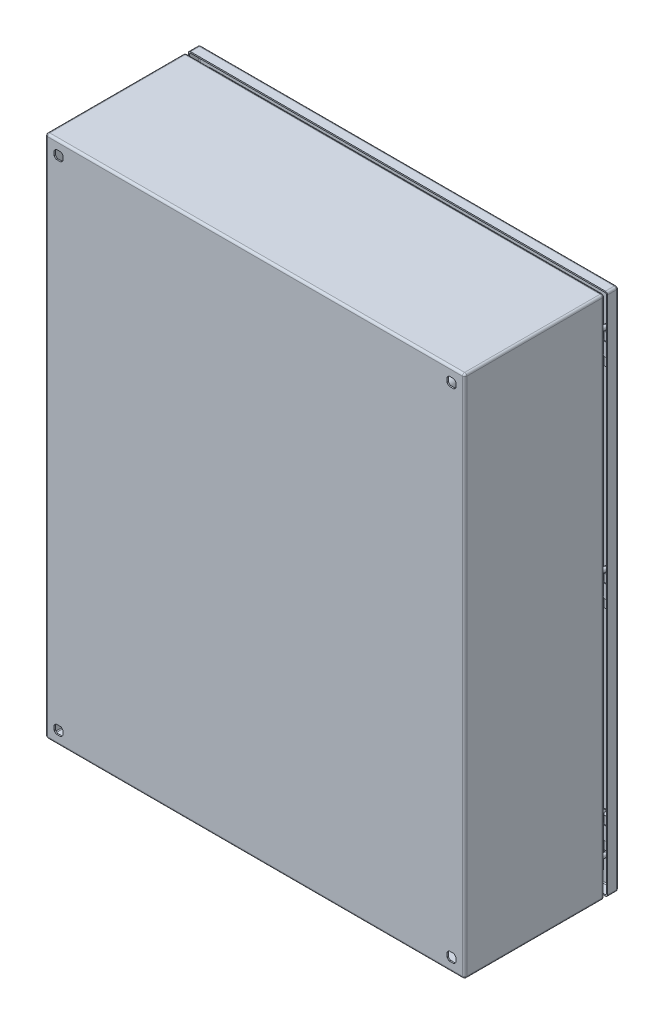
SolidWorks part; units mm, degrees
ref_plane "Front Plane" through (0, 0, 0) normal (0, 0, 1) x (1, 0, 0)
ref_plane "Top Plane" through (0, 0, 0) normal (0, 1, 0) x (1, 0, 0)
ref_plane "Right Plane" through (0, 0, 0) normal (1, 0, 0) x (0, 0, -1)
sketch "Sketch1" plane through (0, 0, 0) normal (0, 0, 1) x (1, 0, 0)
  line L0 (-304.8, -381) -> (304.8, 381) construction
  line L1 (-304.8, 381) -> (304.8, 381)
  line L2 (-304.8, 381) -> (-304.8, -381)
  line L3 (-304.8, -381) -> (304.8, -381)
  line L4 (304.8, 381) -> (304.8, -381)
  line L5 (-258.826, 381) -> (-258.826, -381) construction
  line L6 (-279.4, 355.6) -> (279.4, -355.6) construction
  line L7 (-279.4, 355.6) -> (279.4, 355.6)
  line L8 (-279.4, 355.6) -> (-279.4, -355.6)
  line L9 (-279.4, -355.6) -> (279.4, -355.6)
  line L10 (279.4, 355.6) -> (279.4, -355.6)
  line L11 (221.996, 0) -> (0, 0) construction
  line L12 (-188.214, 321.691) -> (221.996, 321.691)
  line L13 (-188.214, 321.691) -> (-188.214, -321.691)
  line L14 (-188.214, -321.691) -> (221.996, -321.691)
  line L15 (221.996, 321.691) -> (221.996, -321.691)
  line L16 (0, -361.95) -> (0, 361.95) construction
  line L17 (-289.0088, 368.3) -> (-282.4912, 368.3)
  line L18 (-292.1, 365.2088) -> (-292.1, 358.6912)
  line L19 (-289.0088, 355.6) -> (-282.4912, 355.6)
  line L20 (-279.4, 365.2088) -> (-279.4, 358.6912)
  line L21 (-285.75, 361.95) -> (285.75, 361.95) construction
  line L22 (-285.75, 361.95) -> (-285.75, -361.95) construction
  line L23 (-285.75, -361.95) -> (285.75, -361.95) construction
  line L24 (285.75, 361.95) -> (285.75, -361.95) construction
  line L25 (-285.75, 0) -> (285.75, 0) construction
  line L26 (279.4, 365.2088) -> (279.4, 358.6912)
  line L27 (289.0088, 355.6) -> (282.4912, 355.6)
  line L28 (292.1, 365.2088) -> (292.1, 358.6912)
  line L29 (289.0088, 368.3) -> (282.4912, 368.3)
  line L30 (289.0088, -368.3) -> (282.4912, -368.3)
  line L31 (292.1, -365.2088) -> (292.1, -358.6912)
  line L32 (289.0088, -355.6) -> (282.4912, -355.6)
  line L33 (279.4, -365.2088) -> (279.4, -358.6912)
  line L34 (-279.4, -365.2088) -> (-279.4, -358.6912)
  line L35 (-289.0088, -355.6) -> (-282.4912, -355.6)
  line L36 (-292.1, -365.2088) -> (-292.1, -358.6912)
  line L37 (-289.0088, -368.3) -> (-282.4912, -368.3)
  line L38 (-269.113, -345.313) -> (269.113, -345.313) construction
  line L39 (0, -345.313) -> (0, 0) construction
  line L40 (-269.113, -345.313) -> (-269.113, 345.313) construction
  line L41 (-269.113, 0) -> (0, 0) construction
  arc A0 (-289.0088, 368.3) -> (-292.1, 365.2088) centre (-285.75, 361.95) ccw
  arc A1 (-292.1, 358.6912) -> (-289.0088, 355.6) centre (-285.75, 361.95) ccw
  arc A2 (-282.4912, 355.6) -> (-279.4, 358.6912) centre (-285.75, 361.95) ccw
  arc A3 (-279.4, 365.2088) -> (-282.4912, 368.3) centre (-285.75, 361.95) ccw
  arc A4 (279.4, 365.2088) -> (282.4912, 368.3) centre (285.75, 361.95) cw
  arc A5 (282.4912, 355.6) -> (279.4, 358.6912) centre (285.75, 361.95) cw
  arc A6 (292.1, 358.6912) -> (289.0088, 355.6) centre (285.75, 361.95) cw
  arc A7 (289.0088, 368.3) -> (292.1, 365.2088) centre (285.75, 361.95) cw
  arc A8 (289.0088, -368.3) -> (292.1, -365.2088) centre (285.75, -361.95) ccw
  arc A9 (292.1, -358.6912) -> (289.0088, -355.6) centre (285.75, -361.95) ccw
  arc A10 (282.4912, -355.6) -> (279.4, -358.6912) centre (285.75, -361.95) ccw
  arc A11 (279.4, -365.2088) -> (282.4912, -368.3) centre (285.75, -361.95) ccw
  arc A12 (-279.4, -365.2088) -> (-282.4912, -368.3) centre (-285.75, -361.95) cw
  arc A13 (-282.4912, -355.6) -> (-279.4, -358.6912) centre (-285.75, -361.95) cw
  arc A14 (-292.1, -358.6912) -> (-289.0088, -355.6) centre (-285.75, -361.95) cw
  arc A15 (-289.0088, -368.3) -> (-292.1, -365.2088) centre (-285.75, -361.95) cw
  circle A16 centre (-269.113, 345.313) radius 3.9688
  circle A17 centre (269.113, 345.313) radius 3.9688
  circle A18 centre (-269.113, -345.313) radius 3.9688
  circle A19 centre (269.113, -345.313) radius 3.9688
  point P7 (-304.8, 0)
  point P8 (-304.8, 304.8)
  point P9 (-304.8, -304.8)
  dimension "D5" = 14.2748
  dimension "D10" = 82.804
  dimension "D11" = 45.974
  dimension "D12" = 7.9375
  dimension "B" = 609.6
  dimension "D2" = 76.2
  dimension "A" = 762
  dimension "D3" = 76.2
  dimension "D4" = 12.7
  dimension "Panel Width" = 558.8
  dimension "Panel Height" = 711.2
  dimension "H" = 410.21
  dimension "G" = 643.382
  dimension "D6" = 538.226
  dimension "D7" = 690.626
  dimension "D8" = 19.05
  dimension "D9" = 19.05
  dimension "D13" = 116.586
sketch "Sketch2" plane through (0, 0, 0) normal (0, 1, 0) x (1, 0, 0)
  line L0 (0, 0) -> (0, 203.2) construction
  line L1 (0, 203.2) -> (0, 223.901) construction
  point P3 (0, 201.295)
  point P4 (0, 223.901)
  point P5 (0, 219.6148)
  point P7 (0, 214.2127)
  dimension "D1" = 22.606
  dimension "C" = 203.2
  dimension "wall thickness" = 1.905
  dimension "D3" = 4.2862
  dimension "D4" = 12.9177
sketch "Sketch3" plane through (0, 0, 0) normal (0, 0, 1) x (1, 0, 0)
  line L0 (-304.8, 381) -> (-304.8, -381) construction
  line L1 (-304.8, 381) -> (304.8, 381) construction
  line L2 (304.8, 381) -> (304.8, -381) construction
  line L3 (-304.8, -381) -> (304.8, -381) construction
  line L4 (-304.8, 381) -> (-304.8, -381)
  line L5 (-304.8, 381) -> (304.8, 381)
  line L6 (304.8, 381) -> (304.8, -381)
  line L7 (-304.8, -381) -> (304.8, -381)
extrude "Extrude1" add sketch "Sketch3" against normal up to vertex (203.2 mm away) up to point (0, 0, -203.2)
sketch "Sketch4" plane through (0, 0, -203.2) normal (0, 0, -1) x (-1, 0, 0)
  line L4 (285.877, 362.077) -> (-285.877, 362.077)
  line L5 (-285.877, 362.077) -> (-285.877, -362.077)
  line L6 (-285.877, -362.077) -> (285.877, -362.077)
  line L7 (285.877, -362.077) -> (285.877, 362.077)
  line L8 (283.972, 360.172) -> (-283.972, 360.172)
  line L9 (-283.972, 360.172) -> (-283.972, -360.172)
  line L10 (-283.972, -360.172) -> (283.972, -360.172)
  line L11 (283.972, -360.172) -> (283.972, 360.172)
  line L12 (283.972, 360.172) -> (-283.972, 360.172) construction
  line L13 (-283.972, 360.172) -> (-283.972, -360.172) construction
  line L14 (-283.972, -360.172) -> (283.972, -360.172) construction
  line L15 (283.972, -360.172) -> (283.972, 360.172) construction
  dimension "D1" = 20.828
  dimension "D2" = 1.905
extrude "Extrude2" add sketch "Sketch4" along normal up to vertex (11.0127 mm away) up to point (0, 0, -214.2127)
sketch "Sketch5" plane through (0, 0, -214.2127) normal (0, 0, -1) x (-1, 0, 0)
  line L4 (285.877, -362.077) -> (285.877, 362.077)
  line L5 (285.877, 362.077) -> (-285.877, 362.077)
  line L6 (-285.877, 362.077) -> (-285.877, -362.077)
  line L7 (-285.877, -362.077) -> (285.877, -362.077)
  line L8 (285.877, -362.077) -> (285.877, 362.077)
  line L9 (285.877, 362.077) -> (-285.877, 362.077)
  line L10 (-285.877, 362.077) -> (-285.877, -362.077)
  line L11 (-285.877, -362.077) -> (285.877, -362.077)
  dimension "D1" = 0
extrude "Extrude3" add sketch "Sketch5" along normal up to vertex (5.402 mm away) draft 13 up to point (0, 0, -219.6148) draft outward yes
fillet "Fillet1" radius 3.175 20 edges at (304.8, 0, 0) (0, -381, 0) (-304.8, 0, 0) (0, 381, 0) (285.877, -362.077, -208.7064) (286.5006, -362.7006, -216.9137) (-285.877, -362.077, -208.7064) (-286.5006, -362.7006, -216.9137) (286.5006, 362.7006, -216.9137) (285.877, 362.077, -208.7064) (-286.5006, 362.7006, -216.9137) (-285.877, 362.077, -208.7064) (0, -381, -203.2) (304.8, 0, -203.2) (0, 381, -203.2) (-304.8, 0, -203.2) (-304.8, 381, -101.6) (304.8, 381, -101.6) (-304.8, -381, -101.6) (304.8, -381, -101.6)
fillet "Fillet2" radius 1.5875 8 edges at (-284.9471, -361.1471, -203.2) (0, -362.077, -203.2) (284.9471, -361.1471, -203.2) (285.877, 0, -203.2) (284.9471, 361.1471, -203.2) (0, 362.077, -203.2) (-284.9471, 361.1471, -203.2) (-285.877, 0, -203.2)
shell "Shell1" thickness 1.905
sketch "Sketch6" plane through (0, 0, -1.905) normal (0, 0, -1) x (-1, 0, 0)
  line L0 (292.1, 365.2088) -> (292.1, 358.6912) construction
  line L1 (289.0088, 368.3) -> (282.4912, 368.3) construction
  line L2 (-279.4, 365.2088) -> (-279.4, 358.6912) construction
  line L3 (-289.0088, 355.6) -> (-282.4912, 355.6) construction
  line L4 (-292.1, 365.2088) -> (-292.1, 358.6912) construction
  line L5 (-289.0088, 368.3) -> (-282.4912, 368.3) construction
  line L6 (292.1, 365.2088) -> (292.1, 358.6912)
  line L7 (289.0088, 368.3) -> (282.4912, 368.3)
  line L8 (-279.4, 365.2088) -> (-279.4, 358.6912)
  line L9 (-289.0088, 355.6) -> (-282.4912, 355.6)
  line L10 (-292.1, 365.2088) -> (-292.1, 358.6912)
  line L11 (-289.0088, 368.3) -> (-282.4912, 368.3)
  line L12 (279.4, 365.2088) -> (279.4, 358.6912) construction
  line L13 (289.0088, 355.6) -> (282.4912, 355.6) construction
  line L14 (279.4, 365.2088) -> (279.4, 358.6912)
  line L15 (289.0088, 355.6) -> (282.4912, 355.6)
  line L16 (279.4, -365.2088) -> (279.4, -358.6912) construction
  line L17 (289.0088, -355.6) -> (282.4912, -355.6) construction
  line L18 (292.1, -365.2088) -> (292.1, -358.6912) construction
  line L19 (289.0088, -368.3) -> (282.4912, -368.3) construction
  line L20 (279.4, -365.2088) -> (279.4, -358.6912)
  line L21 (289.0088, -355.6) -> (282.4912, -355.6)
  line L22 (292.1, -365.2088) -> (292.1, -358.6912)
  line L23 (289.0088, -368.3) -> (282.4912, -368.3)
  line L24 (-289.0088, -368.3) -> (-282.4912, -368.3) construction
  line L25 (-279.4, -365.2088) -> (-279.4, -358.6912) construction
  line L26 (-289.0088, -355.6) -> (-282.4912, -355.6) construction
  line L27 (-292.1, -365.2088) -> (-292.1, -358.6912) construction
  line L28 (-289.0088, -368.3) -> (-282.4912, -368.3)
  line L29 (-279.4, -365.2088) -> (-279.4, -358.6912)
  line L30 (-289.0088, -355.6) -> (-282.4912, -355.6)
  line L31 (-292.1, -365.2088) -> (-292.1, -358.6912)
  arc A0 (289.0088, 355.6) -> (292.1, 358.6912) centre (285.75, 361.95) ccw construction
  arc A1 (282.4912, 368.3) -> (279.4, 365.2088) centre (285.75, 361.95) ccw construction
  arc A2 (-282.4912, 355.6) -> (-279.4, 358.6912) centre (-285.75, 361.95) ccw construction
  arc A3 (-292.1, 358.6912) -> (-289.0088, 355.6) centre (-285.75, 361.95) ccw construction
  arc A4 (-289.0088, 368.3) -> (-292.1, 365.2088) centre (-285.75, 361.95) ccw construction
  arc A5 (289.0088, 355.6) -> (292.1, 358.6912) centre (285.75, 361.95) ccw
  arc A6 (282.4912, 368.3) -> (279.4, 365.2088) centre (285.75, 361.95) ccw
  arc A7 (-282.4912, 355.6) -> (-279.4, 358.6912) centre (-285.75, 361.95) ccw
  arc A8 (-292.1, 358.6912) -> (-289.0088, 355.6) centre (-285.75, 361.95) ccw
  arc A9 (-289.0088, 368.3) -> (-292.1, 365.2088) centre (-285.75, 361.95) ccw
  arc A10 (279.4, 358.6912) -> (282.4912, 355.6) centre (285.75, 361.95) ccw construction
  arc A11 (292.1, 365.2088) -> (289.0088, 368.3) centre (285.75, 361.95) ccw construction
  arc A12 (279.4, 358.6912) -> (282.4912, 355.6) centre (285.75, 361.95) ccw
  arc A13 (292.1, 365.2088) -> (289.0088, 368.3) centre (285.75, 361.95) ccw
  arc A14 (282.4912, -355.6) -> (279.4, -358.6912) centre (285.75, -361.95) ccw construction
  arc A15 (292.1, -358.6912) -> (289.0088, -355.6) centre (285.75, -361.95) ccw construction
  arc A16 (289.0088, -368.3) -> (292.1, -365.2088) centre (285.75, -361.95) ccw construction
  arc A17 (279.4, -365.2088) -> (282.4912, -368.3) centre (285.75, -361.95) ccw construction
  arc A18 (282.4912, -355.6) -> (279.4, -358.6912) centre (285.75, -361.95) ccw
  arc A19 (292.1, -358.6912) -> (289.0088, -355.6) centre (285.75, -361.95) ccw
  arc A20 (289.0088, -368.3) -> (292.1, -365.2088) centre (285.75, -361.95) ccw
  arc A21 (279.4, -365.2088) -> (282.4912, -368.3) centre (285.75, -361.95) ccw
  arc A22 (-282.4912, -368.3) -> (-279.4, -365.2088) centre (-285.75, -361.95) ccw construction
  arc A23 (-279.4, -358.6912) -> (-282.4912, -355.6) centre (-285.75, -361.95) ccw construction
  arc A24 (-289.0088, -355.6) -> (-292.1, -358.6912) centre (-285.75, -361.95) ccw construction
  arc A25 (-292.1, -365.2088) -> (-289.0088, -368.3) centre (-285.75, -361.95) ccw construction
  arc A26 (-282.4912, -368.3) -> (-279.4, -365.2088) centre (-285.75, -361.95) ccw
  arc A27 (-279.4, -358.6912) -> (-282.4912, -355.6) centre (-285.75, -361.95) ccw
  arc A28 (-289.0088, -355.6) -> (-292.1, -358.6912) centre (-285.75, -361.95) ccw
  arc A29 (-292.1, -365.2088) -> (-289.0088, -368.3) centre (-285.75, -361.95) ccw
  arc A30 (-279.4, 365.2088) -> (-282.4912, 368.3) centre (-285.75, 361.95) ccw construction
  arc A31 (-279.4, 365.2088) -> (-282.4912, 368.3) centre (-285.75, 361.95) ccw
extrude "Cut-Extrude1" cut sketch "Sketch6" against normal through all
ref_plane "Plane1" through (0, 0, -23.876) normal (0, 0, 1) x (1, 0, 0)
sketch "Sketch7" plane through (0, 0, -23.876) normal (0, 0, 1) x (1, 0, 0)
  line L0 (-279.4, -355.6) -> (279.4, -355.6) construction
  line L1 (-279.4, 355.6) -> (-279.4, -355.6) construction
  line L2 (-279.4, 355.6) -> (279.4, 355.6) construction
  line L3 (279.4, 355.6) -> (279.4, -355.6) construction
  line L4 (-279.4, -355.6) -> (279.4, -355.6)
  line L5 (-279.4, 355.6) -> (-279.4, -355.6)
  line L6 (-279.4, 355.6) -> (279.4, 355.6)
  line L7 (279.4, 355.6) -> (279.4, -355.6)
  circle A0 centre (269.113, -345.313) radius 3.9688 construction
  circle A1 centre (-269.113, -345.313) radius 3.9688 construction
  circle A2 centre (-269.113, 345.313) radius 3.9688 construction
  circle A3 centre (269.113, 345.313) radius 3.9688 construction
  circle A4 centre (269.113, -345.313) radius 3.9688
  circle A5 centre (-269.113, -345.313) radius 3.9688
  circle A6 centre (-269.113, 345.313) radius 3.9688
  circle A7 centre (269.113, 345.313) radius 3.9688
extrude "Extrude4" add sketch "Sketch7" against normal blind 1.524
sketch "Sketch8" plane through (0, 0, -1.905) normal (0, 0, -1) x (-1, 0, 0)
  circle A0 centre (-269.113, 345.313) radius 7.9375
  circle A1 centre (269.113, 345.313) radius 7.9375
  circle A2 centre (269.113, -345.313) radius 7.9375
  circle A3 centre (-269.113, -345.313) radius 7.9375
  circle A4 centre (-269.113, 345.313) radius 3.9688 construction
  circle A5 centre (269.113, 345.313) radius 3.9688 construction
  circle A6 centre (-269.113, 345.313) radius 3.9688
  circle A7 centre (269.113, 345.313) radius 3.9688
  circle A8 centre (269.113, -345.313) radius 3.9688 construction
  circle A9 centre (269.113, -345.313) radius 3.9688
  circle A10 centre (-269.113, -345.313) radius 3.9688 construction
  circle A11 centre (-269.113, -345.313) radius 3.9688
  dimension "D1" = 15.875
extrude "Extrude5" add sketch "Sketch8" along normal up to surface (21.971 mm away) up to plane "Plane1"
ref_plane "Plane2" through (0, 0, -223.901) normal (0, 0, 1) x (1, 0, 0)
sketch "Sketch9" plane through (0, 0, -223.901) normal (0, 0, 1) x (1, 0, 0)
  line L0 (-304.8, -381) -> (304.8, -381) construction
  line L1 (304.8, 381) -> (304.8, -381) construction
  line L2 (-304.8, 381) -> (-304.8, -381) construction
  line L3 (-304.8, 381) -> (304.8, 381) construction
  line L4 (-304.8, -381) -> (304.8, -381)
  line L5 (304.8, 381) -> (304.8, -381)
  line L6 (-304.8, 381) -> (-304.8, -381)
  line L7 (-304.8, 381) -> (304.8, 381)
extrude "Extrude6" add sketch "Sketch9" along normal blind 16.002 separate body
fillet "Fillet3" radius 3.175 8 edges at (0, -381, -223.901) (304.8, 0, -223.901) (0, 381, -223.901) (-304.8, 0, -223.901) (304.8, -381, -215.9) (-304.8, -381, -215.9) (304.8, 381, -215.9) (-304.8, 381, -215.9)
shell "Shell2" thickness 1.905
sketch "Sketch10" plane through (0, 0, -221.996) normal (0, 0, 1) x (1, 0, 0)
  line L0 (-188.214, -321.691) -> (221.996, -321.691) construction
  line L1 (221.996, 321.691) -> (221.996, -321.691) construction
  line L2 (-188.214, 321.691) -> (221.996, 321.691) construction
  line L3 (-188.214, 321.691) -> (-188.214, -321.691) construction
  line L4 (-181.864, -321.691) -> (215.646, -321.691)
  line L5 (221.996, 315.341) -> (221.996, -315.341)
  line L6 (-181.864, 321.691) -> (215.646, 321.691)
  line L7 (-188.214, 315.341) -> (-188.214, -315.341)
  arc A0 (-181.864, 321.691) -> (-188.214, 315.341) centre (-181.864, 315.341) ccw
  arc A1 (221.996, 315.341) -> (215.646, 321.691) centre (215.646, 315.341) ccw
  arc A2 (215.646, -321.691) -> (221.996, -315.341) centre (215.646, -315.341) ccw
  arc A3 (-181.864, -321.691) -> (-188.214, -315.341) centre (-181.864, -315.341) cw
  dimension "D1" = 6.35
extrude "Cut-Extrude2" cut sketch "Sketch10" against normal through all
sketch "Sketch11" plane through (0, 0, -223.901) normal (0, 0, -1) x (-1, 0, 0)
  line L8 (181.864, 321.183) -> (-215.646, 321.183)
  line L9 (-221.488, 315.341) -> (-221.488, -315.341)
  line L10 (-215.646, -321.183) -> (181.864, -321.183)
  line L11 (187.706, -315.341) -> (187.706, 315.341)
  line L12 (181.864, 321.183) -> (-215.646, 321.183)
  line L13 (-221.488, 315.341) -> (-221.488, -315.341)
  line L14 (-215.646, -321.183) -> (181.864, -321.183)
  line L15 (187.706, -315.341) -> (187.706, 315.341)
  arc A8 (-215.646, 321.183) -> (-221.488, 315.341) centre (-215.646, 315.341) ccw
  arc A9 (-221.488, -315.341) -> (-215.646, -321.183) centre (-215.646, -315.341) ccw
  arc A10 (181.864, -321.183) -> (187.706, -315.341) centre (181.864, -315.341) ccw
  arc A11 (187.706, 315.341) -> (181.864, 321.183) centre (181.864, 315.341) ccw
  arc A12 (-215.646, 321.183) -> (-221.488, 315.341) centre (-215.646, 315.341) ccw
  arc A13 (-221.488, -315.341) -> (-215.646, -321.183) centre (-215.646, -315.341) ccw
  arc A14 (181.864, -321.183) -> (187.706, -315.341) centre (181.864, -315.341) ccw
  arc A15 (187.706, 315.341) -> (181.864, 321.183) centre (181.864, 315.341) ccw
  dimension "D1" = 0.508
extrude "Extrude7" add sketch "Sketch11" against normal blind 3.048
fillet "Fillet4" radius 0.762 8 edges at (-187.706, 0, -223.901) (-185.9949, -319.4719, -223.901) (16.891, -321.183, -223.901) (219.7769, -319.4719, -223.901) (221.488, 0, -223.901) (219.7769, 319.4719, -223.901) (16.891, 321.183, -223.901) (-185.9949, 319.4719, -223.901)
sketch "Sketch12" plane through (0, 0, -220.853) normal (0, 0, 1) x (1, 0, 0)
  line L8 (-200.406, 315.341) -> (-200.406, -315.341)
  line L9 (-181.864, -333.883) -> (215.646, -333.883)
  line L10 (234.188, -315.341) -> (234.188, 315.341)
  line L11 (215.646, 333.883) -> (-181.864, 333.883)
  line L12 (-200.406, 315.341) -> (-200.406, -315.341)
  line L13 (-181.864, -333.883) -> (215.646, -333.883)
  line L14 (234.188, -315.341) -> (234.188, 315.341)
  line L15 (215.646, 333.883) -> (-181.864, 333.883)
  arc A8 (-181.864, 333.883) -> (-200.406, 315.341) centre (-181.864, 315.341) ccw
  arc A9 (-200.406, -315.341) -> (-181.864, -333.883) centre (-181.864, -315.341) ccw
  arc A10 (215.646, -333.883) -> (234.188, -315.341) centre (215.646, -315.341) ccw
  arc A11 (234.188, 315.341) -> (215.646, 333.883) centre (215.646, 315.341) ccw
  arc A12 (-181.864, 333.883) -> (-200.406, 315.341) centre (-181.864, 315.341) ccw
  arc A13 (-200.406, -315.341) -> (-181.864, -333.883) centre (-181.864, -315.341) ccw
  arc A14 (215.646, -333.883) -> (234.188, -315.341) centre (215.646, -315.341) ccw
  arc A15 (234.188, 315.341) -> (215.646, 333.883) centre (215.646, 315.341) ccw
  dimension "D1" = 12.7
extrude "Extrude8" add sketch "Sketch12" along normal blind 1.524
ref_plane "Plane3" through (0, -304.8, 0) normal (0, 1, 0) x (-1, 0, 0)
sketch "Sketch13" plane through (0, -304.8, 0) normal (0, 1, 0) x (-1, 0, 0)
  line L0 (-297.942, -220.1418) -> (-290.7313, -220.1418)
  line L1 (-287.8582, -203.2) -> (-289.2044, -203.2)
  line L2 (-287.019, -217.1889) -> (-285.877, -212.2424)
  line L3 (-285.877, -212.2424) -> (-285.877, -205.1812)
  line L4 (-297.942, -218.694) -> (-290.7313, -218.694)
  line L5 (-288.4297, -216.8632) -> (-287.3248, -212.0774)
  line L6 (-287.3248, -212.0774) -> (-287.3248, -205.1812)
  line L7 (-287.8582, -204.6478) -> (-289.2044, -204.6478)
  line L8 (-289.2044, -203.2) -> (-289.2044, -204.6478)
  line L9 (-295.5394, -217.5372) -> (-294.4076, -218.44)
  line L10 (-301.625, -203.2) -> (301.625, -203.2) construction
  line L13 (-285.877, -204.7875) -> (-285.877, -214.2127) construction
  arc A0 (-294.4076, -218.44) -> (-297.942, -220.1418) centre (-297.942, -215.6206) ccw
  arc A1 (-290.7313, -220.1418) -> (-287.019, -217.1889) centre (-290.7313, -216.3318) ccw
  arc A2 (-285.877, -205.1812) -> (-287.8582, -203.2) centre (-287.8582, -205.1812) ccw
  arc A3 (-290.7313, -218.694) -> (-288.4297, -216.8632) centre (-290.7313, -216.3318) ccw
  arc A4 (-287.3248, -205.1812) -> (-287.8582, -204.6478) centre (-287.8582, -205.1812) ccw
  arc A5 (-295.5394, -217.5372) -> (-297.942, -218.694) centre (-297.942, -215.6206) ccw
  point P11 (-285.877, -203.2)
  dimension "D2" = 9.0424
  dimension "D4" = 3.81
  dimension "D7" = 1.9812
  dimension "D1" = 12.065
  dimension "D3" = 13
  dimension "D5" = 16.9418
  dimension "D6" = 3.3274
  dimension "D9" = 0.254
  dimension "D8" = 7.0612
  dimension "D10" = 1.4478
extrude "Extrude9" add sketch "Sketch13" along normal mid plane 43.9928 separate body
sketch "Sketch14" plane through (0, -304.8, 0) normal (0, 1, 0) x (-1, 0, 0)
  line L0 (-297.942, -220.1418) -> (-290.7313, -220.1418) construction
  line L1 (-302.4632, -220.1418) -> (-290.7313, -220.1418)
  line L2 (-302.4632, -220.1418) -> (-302.4632, -211.0994)
  line L3 (-302.4632, -211.0994) -> (-290.7313, -211.0994)
  line L4 (-290.7313, -220.1418) -> (-290.7313, -211.0994)
  arc A0 (-294.4076, -218.44) -> (-297.942, -220.1418) centre (-297.942, -215.6206) ccw construction
extrude "Cut-Extrude3" cut sketch "Sketch14" against normal mid plane 20.574
sketch "Sketch15" plane through (0, -294.513, 0) normal (0, -1, 0) x (1, 0, 0)
  circle A0 centre (297.942, -215.6206) radius 5.08
  circle A1 centre (297.942, -215.6206) radius 3.0734
  arc A2 (297.942, -218.694) -> (295.5394, -217.5372) centre (297.942, -215.6206) ccw construction
  dimension "D1" = 10.16
extrude "Extrude10" add sketch "Sketch15" along normal up to vertex (20.574 mm away) separate body up to point (290.7313, -315.087, -220.1418)
chamfer "Chamfer1" distance 0.508 angle 45 2 edges at (297.942, -294.513, -220.7006) (297.942, -315.087, -220.7006)
sketch "Sketch16" plane through (0, -326.7964, 0) normal (0, -1, 0) x (1, 0, 0)
  circle A0 centre (297.942, -215.6206) radius 3.0734
  arc A1 (297.942, -218.694) -> (295.5394, -217.5372) centre (297.942, -215.6206) ccw construction
extrude "Extrude11" add sketch "Sketch16" against normal up to vertex (43.9928 mm away) up to point (297.942, -282.8036, -220.1418)
sketch "Sketch17" plane through (0, -326.7964, 0) normal (0, -1, 0) x (1, 0, 0)
  circle A1 centre (297.942, -215.6206) radius 3.0734
  circle A2 centre (297.942, -215.6206) radius 3.0734
  dimension "D1" = 0
extrude "Extrude12" add sketch "Sketch17" along normal blind 1.524
sketch "Sketch18" plane through (0, -328.3204, 0) normal (0, -1, 0) x (1, 0, 0)
  line L0 (142.7154, -211.6582) -> (148.689, -211.6582) construction
  circle A1 centre (297.942, -215.6206) radius 3.0734
  circle A2 centre (297.942, -215.6206) radius 3.0734
  dimension "D2" = 3.9624
  dimension "D1" = 0
revolve "Revolve1" add sketch "Sketch18" angle 90 about L0
sketch "Sketch19" plane through (0, 0, -211.6582) normal (0, 0, 1) x (1, 0, 0)
  circle A1 centre (297.942, -332.2828) radius 3.0734
  circle A2 centre (297.942, -332.2828) radius 3.0734
  dimension "D1" = 0
extrude "Extrude13" add sketch "Sketch19" along normal blind 6.35
mirror "Mirror1" about plane through (0, 0, 0) normal (0, 1, 0) of bodies 117
pattern_linear "LPattern2" count 2 spacing 304.8 along (0, -1, 0) of bodies 123
sketch "Sketch21" plane through (0, 0, -223.901) normal (0, 0, -1) x (-1, 0, 0)
  line L0 (285.75, 0) -> (-285.75, 0) construction
  line L1 (258.826, 381) -> (258.826, -381) construction
  circle A0 centre (258.826, 0) radius 13.97
  dimension "D1" = 27.94
extrude "Extrude14" add sketch "Sketch21" along normal blind 2.286 separate body
sketch "Sketch22" plane through (0, 0, -226.187) normal (0, 0, -1) x (-1, 0, 0)
  circle A1 centre (258.826, 0) radius 13.97
  circle A2 centre (258.826, 0) radius 13.97
  dimension "D1" = 0
extrude "Extrude15" add sketch "Sketch22" along normal blind 3.175 draft 45
sketch "Sketch23" plane through (0, 0, -229.362) normal (0, 0, -1) x (-1, 0, 0)
  line L0 (258.826, 381) -> (258.826, -381) construction
  circle A0 centre (258.826, 0) radius 8.7313
  dimension "D1" = 17.4625
extrude "Cut-Extrude4" cut sketch "Sketch23" against normal blind 1.524
chamfer "Chamfer2" distance 0.381 angle 45 1 edges at (-267.5573, 0, -229.362)
sketch "Sketch24" plane through (0, 0, -227.838) normal (0, 0, -1) x (-1, 0, 0)
  circle A2 centre (258.826, 0) radius 8.3503
  circle A3 centre (258.826, 0) radius 8.3503
  dimension "D1" = 0.381
extrude "Extrude16" add sketch "Sketch24" along normal blind 1.524
fillet "Fillet5" radius 0.762 1 edges at (-267.1762, 0, -229.362)
sketch "Sketch25" plane through (0, 0, -229.362) normal (0, 0, -1) x (-1, 0, 0)
  line L0 (253.5996, 6.5124) -> (261.8527, -7.7824)
  line L1 (255.7993, 7.7824) -> (264.0524, -6.5124)
  line L2 (258.826, 0) -> (258.826, 4.1848) construction
  line L3 (258.826, 381) -> (258.826, -381) construction
  line L4 (258.826, 0) -> (219.2235, 68.5935) construction
  circle A0 centre (258.826, 0) radius 8.3503 construction
  arc A1 (261.8527, -7.7824) -> (264.0524, -6.5124) centre (258.826, 0) ccw
  arc A2 (255.7993, 7.7824) -> (253.5996, 6.5124) centre (258.826, 0) ccw
  dimension "D1" = 30
  dimension "D2" = 1.27
  dimension "D3" = 1.27
extrude "Cut-Extrude5" cut sketch "Sketch25" against normal blind 1.27
sketch "Sketch26" plane through (0, 0, 0) normal (0, 1, 0) x (1, 0, 0)
  line L4 (-279.4, 23.876) -> (279.4, 23.876)
  line L5 (-279.4, 25.4) -> (-279.4, 23.876)
  line L6 (279.4, 25.4) -> (-279.4, 25.4)
  line L7 (279.4, 23.876) -> (279.4, 25.4)
  line L8 (-279.4, 23.876) -> (279.4, 23.876)
  line L9 (-279.4, 25.4) -> (-279.4, 23.876)
  line L10 (279.4, 25.4) -> (-279.4, 25.4)
  line L11 (279.4, 23.876) -> (279.4, 25.4)
  dimension "D1" = 0
pattern_linear "LPattern1" count 2 spacing 228.6 along (0, 1, 0) of bodies 122
mirror "Mirror2" about plane through (0, 0, 0) normal (0, 1, 0) of bodies 124
delete or keep bodies "Body-Delete1" type delete bodies bodies 122
sketch "Sketch27" plane through (0, 0, -25.4) normal (0, 0, -1) x (-1, 0, 0)
  line L0 (-250.2733, 106.6034) -> (116.5252, 106.6034) construction
  text T0 "IRRIGATION\r\nBOX" font "Arial" height in points 200
extrude "Cut-Extrude6" cut sketch "Sketch27" against normal blind 2.54
equation "\"D6@Sketch1\" = \"B@Sketch1\"-2.81"
equation "\"D7@Sketch1\" = \"A@Sketch1\"-2.81"
equation "\"D3@Sketch2\" = \"wall thickness@Sketch2\"*2.25"
equation "\"D4@Sketch2\" = \"D1@Sketch2\"/1.750"
equation "\"D2@Sketch4\" = \"wall thickness@Sketch2\""
equation "\"D1@Shell1\" = \"wall thickness@Sketch2\""
equation "\"D1@Fillet3\" = \"D1@Fillet1\""
equation "\"D1@Shell2\" = \"wall thickness@Sketch2\""
